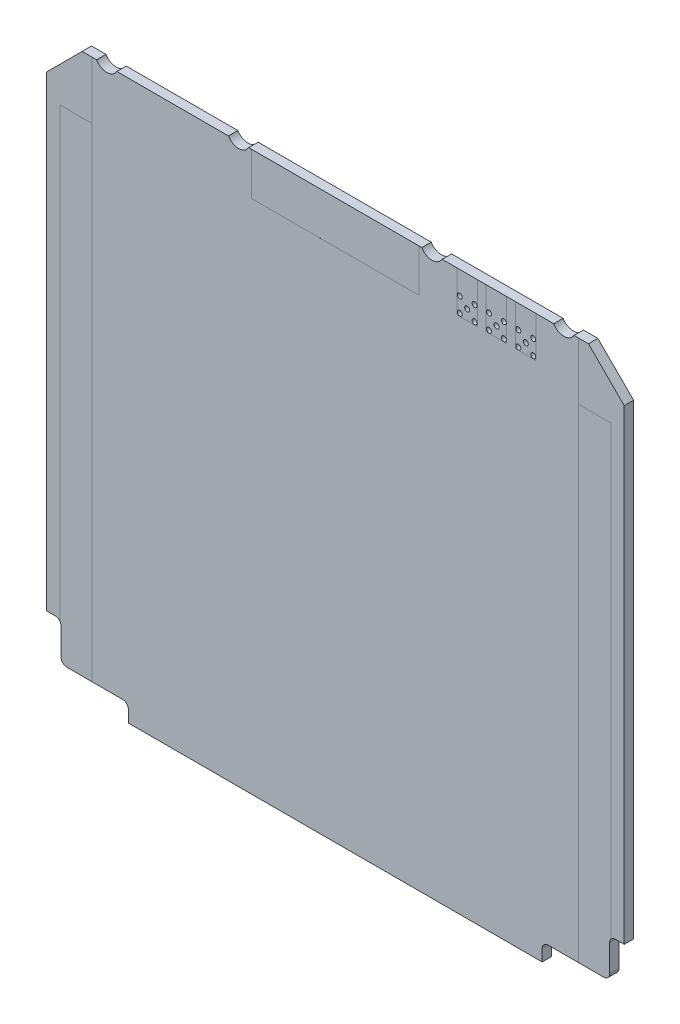
SolidWorks part; units mm, degrees
material "FR4_stuffedProtoboard"
ref_plane "Front Plane" through (0, 0, 0) normal (0, 0, 1) x (1, 0, 0)
ref_plane "Top Plane" through (0, 0, 0) normal (0, 1, 0) x (1, 0, 0)
ref_plane "Right Plane" through (0, 0, 0) normal (1, 0, 0) x (0, 0, -1)
ref_plane "Plane4" through (0, 0, -0.0125) normal (0, 0, -1) x (-1, 0, 0)
sketch "Sketch1" plane through (0, 0, -0.0125) normal (0, 0, -1) x (-1, 0, 0)
  line L4 (49.3, -50) -> (49.3, 45.3)
  line L6 (49.3, 45.3) -> (-49.3, 45.3)
  line L12 (-49.3, 45.3) -> (-49.3, -50)
  line L17 (-49.3, -50) -> (49.3, -50)
  line L18 (0, -50) -> (0, 45.3) construction
  dimension "D7" = 95.3
  dimension "D1" = 98.6
  dimension "D34" = 50
extrude "basicSize" add sketch "Sketch1" against normal blind 1.6
chamfer "Chamfer1" distance 6.1 angle 45 2 edges at (49.3, 45.3, 0.7875) (-49.3, 45.3, 0.7875)
sketch "Sketch4" plane through (0, 0, 1.5875) normal (0, 0, 1) x (1, 0, 0)
  line L1 (37.2679, 45.3) -> (40.7321, 45.3)
  line L7 (-43.2, 45.3) -> (43.2, 45.3) construction
  line L8 (49.3, 39.2) -> (49.3, -50) construction
  arc A0 (40.7321, 45.3) -> (37.2679, 45.3) centre (39, 46.3) cw
  point P5 (39, 44.3)
  dimension "D1" = 2
  dimension "D3" = 10.3
  dimension "D2" = 1
extrude "backplaneSideScrewCutout" cut sketch "Sketch4" against normal through all both and the other way through all
pattern_linear "LPattern3" count 2 spacing 22.5 along (-1, 0, 0) of "backplaneSideScrewCutout"
mirror "Mirror3" about plane through (0, 0, 0) normal (1, 0, 0) of "LPattern3"
sketch "Sketch6" plane through (0, 0, 1.5875) normal (0, 0, 1) x (1, 0, 0)
  line L0 (-49.3, -50) -> (-49.3, 39.2) construction
  line L1 (-49.3, -40.4) -> (-46.8, -40.4)
  line L2 (-49.3, -40.4) -> (-49.3, -50)
  line L4 (-46.8, -40.4) -> (-46.8, -47)
  line L5 (49.3, -50) -> (-49.3, -50) construction
  line L6 (-35.3, -50) -> (-49.3, -50)
  line L7 (-35.3, -50) -> (-35.3, -47)
  line L8 (-35.3, -47) -> (-46.8, -47)
  dimension "D1" = 2.5
  dimension "D2" = 3
  dimension "D3" = 9.6
  dimension "D4" = 14
extrude "Cut-Extrude4" cut sketch "Sketch6" against normal through all
fillet "Fillet1" radius 1 3 edges at (-35.3, -47, 0.7875) (-46.8, -47, 0.7875) (-46.8, -40.4, 0.7875)
mirror "Mirror1" about plane through (0, 0, 0) normal (1, 0, 0) of "Cut-Extrude4", "Fillet1"
sketch "Sketch5" plane through (0, 0, 1.5875) normal (0, 0, 1) x (1, 0, 0)
  line L0 (21.23, 41.37) -> (23.77, 38.83) construction
  line L1 (21.23, 38.83) -> (21.23, 41.37) construction
  line L2 (21.23, 41.37) -> (23.77, 41.37) construction
  line L4 (49.3, 39.2) -> (49.3, -40.4) construction
  line L5 (-14.7679, 45.3) -> (14.7679, 45.3) construction
  circle A0 centre (22.5, 40.1) radius 0.425
  circle A1 centre (21.23, 41.37) radius 0.425
  circle A3 centre (21.23, 38.83) radius 0.425
  circle A4 centre (23.77, 41.37) radius 0.425
  circle A5 centre (23.77, 38.83) radius 0.425
  dimension "D2" = 0.85
  dimension "D1" = 2.54
  dimension "D3" = 3.93
  dimension "D4" = 28.07
extrude "Cut-Extrude3" cut sketch "Sketch5" against normal through all
pattern_linear "LPattern2" count 3 spacing 5 along (1, 0, 0) of "Cut-Extrude3"
sketch "partFootprints" plane through (0, 0, 1.5875) normal (0, 0, 1) x (1, 0, 0)
  line L1 (18.2321, 45.3) -> (37.2679, 45.3) construction
  line L6 (20.75, 45.3) -> (20.75, 38.35)
  line L7 (20.75, 38.35) -> (24.25, 38.35)
  line L8 (24.25, 38.35) -> (24.25, 45.3)
  line L9 (24.25, 45.3) -> (20.75, 45.3)
  line L10 (25.75, 45.3) -> (25.75, 38.35)
  line L11 (25.75, 38.35) -> (29.25, 38.35)
  line L12 (29.25, 38.35) -> (29.25, 45.3)
  line L13 (29.25, 45.3) -> (25.75, 45.3)
  line L14 (30.75, 45.3) -> (30.75, 38.35)
  line L15 (30.75, 38.35) -> (34.25, 38.35)
  line L16 (34.25, 38.35) -> (34.25, 45.3)
  line L17 (34.25, 45.3) -> (30.75, 45.3)
  line L19 (32.5, 38.35) -> (32.5, 40.1) construction
  line L23 (22.5, 38.35) -> (22.5, 40.1) construction
  circle A2 centre (22.5, 40.1) radius 0.425 construction
  circle A5 centre (32.5, 40.1) radius 0.425 construction
  dimension "D1" = 1.75
  dimension "D8" = 3.5
  dimension "D6" = 3
extrude "MMCXfootprint" cut sketch "partFootprints" against normal blind 0.0001
sketch "Sketch7" plane through (0, 0, 1.5875) normal (0, 0, 1) x (1, 0, 0)
  line L0 (-14.2875, 45.5) -> (-14.2875, 39.912) construction
  line L1 (-14.2875, 45.3) -> (-14.2875, 38.007)
  line L2 (-12.2428, 38.007) -> (-11.8872, 38.007) construction
  line L3 (-14.2875, 38.007) -> (14.2875, 38.007)
  line L4 (14.2875, 45.5) -> (14.2875, 39.912) construction
  line L5 (14.2875, 45.3) -> (14.2875, 38.007)
  line L7 (-14.7679, 45.3) -> (14.7679, 45.3) construction
  line L8 (-14.2875, 45.3) -> (14.2875, 45.3)
extrude "TigerEyeFootprint" cut sketch "Sketch7" against normal blind 0.0001
sketch "thermalContacts_upper" plane through (0, 0, 1.5875) normal (0, 0, 1) x (1, 0, 0)
  line L0 (-49.3, -40.4) -> (-49.3, 39.2) construction
  line L1 (35.3, -50) -> (-35.3, -50) construction
  line L2 (-49.3, 45.3) -> (49.3, 45.3) construction
  line L3 (-47, 35.5) -> (-47, -41.5)
  line L5 (-41.5, 35.5) -> (-47, 35.5)
  line L18 (-41.5, 35.5) -> (-41.5, 47)
  line L23 (-41.5, 47) -> (-56.1922, 47)
  line L24 (-56.1922, 47) -> (-56.1922, -41.5)
  line L25 (-56.1922, -41.5) -> (-47, -41.5)
  dimension "D1" = 2.3
  dimension "D2" = 8.5
  dimension "D3" = 9.8
  dimension "D4" = 7.8
  dimension "D5" = 88.5
  dimension "D6" = 14.6922
extrude "keepOut_bottom" cut sketch "thermalContacts_upper" against normal blind 0.0001
sketch "Sketch3" plane through (0, 0, 1.5875) normal (0, 0, 1) x (1, 0, 0)
  line L0 (18.2321, 45.3) -> (20.75, 45.3) construction
  line L1 (-46.8, -46) -> (-46.8, -41.4) construction
  line L2 (-36.3, -47) -> (-45.8, -47) construction
  line L3 (-47, -40.8) -> (-47, 35.5) construction
  line L10 (0, -50) -> (0, 45.3) construction
  line L11 (35.3, -50) -> (-35.3, -50) construction
  line L13 (-41.5, 35.5) -> (-47, 35.5)
  line L14 (-45.8, -47) -> (-41.5, -47)
  line L15 (-46.8, -41.4) -> (-46.8, -46)
  line L16 (-47, 35.5) -> (-47, -40.8)
  line L17 (-41.5, -47) -> (-41.5, 35.5)
  arc A2 (-46.8, -41.4) -> (-47, -40.8) centre (-47.8, -41.4) ccw construction
  arc A3 (-46.8, -46) -> (-45.8, -47) centre (-45.8, -46) ccw construction
  arc A4 (-45.8, -47) -> (-46.8, -46) centre (-45.8, -46) cw
  arc A5 (-47, -40.8) -> (-46.8, -41.4) centre (-47.8, -41.4) cw
extrude "caution_top" cut sketch "Sketch3" against normal blind 0.0001
ref_plane "midplane_Z" through (0, 0, 0.7875) normal (0, 0, 1) x (1, 0, 0)
mirror "clearances_top-bottom" about plane through (0, 0, 0.7875) normal (0, 0, 1) of "keepOut_bottom", "caution_top"
mirror "clearances_side-side" about plane through (0, 0, 0) normal (1, 0, 0) of "clearances_top-bottom"
ref_point "rail midpoint"
